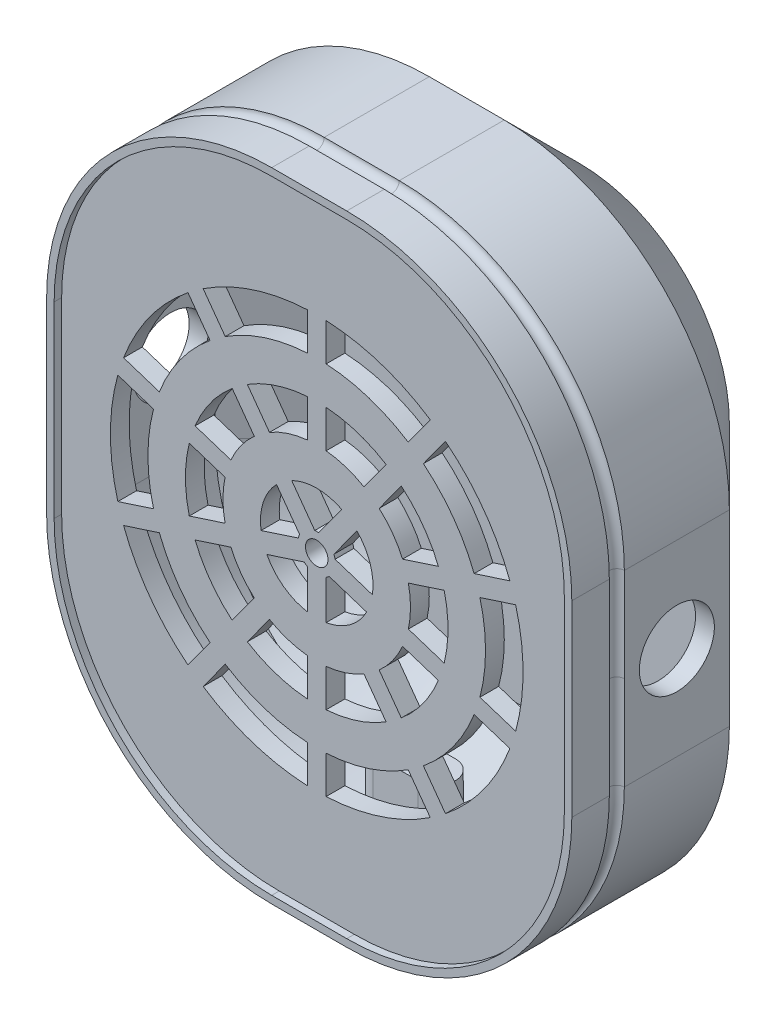
SolidWorks part; units mm, degrees
ref_plane "Front Plane" through (0, 0, 0) normal (0, 0, 1) x (1, 0, 0)
ref_plane "Top Plane" through (0, 0, 0) normal (0, 1, 0) x (1, 0, 0)
ref_plane "Right Plane" through (0, 0, 0) normal (1, 0, 0) x (0, 0, -1)
sketch "Sketch2" plane through (0, 0, 0) normal (0, 0, 1) x (1, 0, 0)
  line L1 (5, -42.5) -> (-5, -42.5)
  line L2 (35, -12.5) -> (35, 12.5)
  line L3 (5, 42.5) -> (-5, 42.5)
  line L4 (-35, -12.5) -> (-35, 12.5)
  line L5 (35, -42.5) -> (-35, 42.5) construction
  line L6 (35, 42.5) -> (-35, -42.5) construction
  arc A0 (-5, -42.5) -> (-35, -12.5) centre (-5, -12.5) cw
  arc A1 (5, -42.5) -> (35, -12.5) centre (5, -12.5) ccw
  arc A2 (35, 12.5) -> (5, 42.5) centre (5, 12.5) ccw
  arc A3 (-5, 42.5) -> (-35, 12.5) centre (-5, 12.5) ccw
  point P0 (0, 0)
  dimension "D1" = 30
extrude "Boss-Extrude1" add sketch "Sketch2" along normal blind 20
sketch "Sketch3" plane through (0, 0, 0) normal (0, 0, -1) x (-1, 0, 0)
  line L8 (25, -12.5) -> (25, 12.5)
  line L9 (5, 32.5) -> (-5, 32.5)
  line L10 (-25, 12.5) -> (-25, -12.5)
  line L11 (-5, -32.5) -> (5, -32.5)
  line L12 (25, -12.5) -> (25, 12.5)
  line L13 (5, 32.5) -> (-5, 32.5)
  line L14 (-25, 12.5) -> (-25, -12.5)
  line L15 (-5, -32.5) -> (5, -32.5)
  arc A8 (5, -32.5) -> (25, -12.5) centre (5, -12.5) ccw
  arc A9 (25, 12.5) -> (5, 32.5) centre (5, 12.5) ccw
  arc A10 (-5, 32.5) -> (-25, 12.5) centre (-5, 12.5) ccw
  arc A11 (-25, -12.5) -> (-5, -32.5) centre (-5, -12.5) ccw
  arc A12 (5, -32.5) -> (25, -12.5) centre (5, -12.5) ccw
  arc A13 (25, 12.5) -> (5, 32.5) centre (5, 12.5) ccw
  arc A14 (-5, 32.5) -> (-25, 12.5) centre (-5, 12.5) ccw
  arc A15 (-25, -12.5) -> (-5, -32.5) centre (-5, -12.5) ccw
  dimension "D1" = 10
extrude "Boss-Extrude2" add sketch "Sketch3" along normal blind 10
chamfer "Chamfer1" distance 10 angle 45 8 edges at (0, -32.5, 0) (-19.1421, -26.6421, 0) (19.1421, -26.6421, 0) (-25, 0, 0) (25, 0, 0) (-19.1421, 26.6421, 0) (19.1421, 26.6421, 0) (0, 32.5, 0)
ref_plane "Plane1" through (0, 0, 15) normal (0, 0, 1) x (1, 0, 0)
sketch "Sketch5" plane through (0, 0, 15) normal (0, 0, 1) x (1, 0, 0)
  line L4 (-5, -42.5) -> (5, -42.5)
  line L5 (35, -12.5) -> (35, 12.5)
  line L6 (5, 42.5) -> (-5, 42.5)
  line L7 (-35, 12.5) -> (-35, -12.5)
  line L8 (-5, -42.5) -> (5, -42.5)
  line L9 (35, -12.5) -> (35, 12.5)
  line L10 (5, 42.5) -> (-5, 42.5)
  line L11 (-35, 12.5) -> (-35, -12.5)
  arc A4 (-35, -12.5) -> (-5, -42.5) centre (-5, -12.5) ccw
  arc A5 (5, -42.5) -> (35, -12.5) centre (5, -12.5) ccw
  arc A6 (35, 12.5) -> (5, 42.5) centre (5, 12.5) ccw
  arc A7 (-5, 42.5) -> (-35, 12.5) centre (-5, 12.5) ccw
  arc A8 (-35, -12.5) -> (-5, -42.5) centre (-5, -12.5) ccw
  arc A9 (5, -42.5) -> (35, -12.5) centre (5, -12.5) ccw
  arc A10 (35, 12.5) -> (5, 42.5) centre (5, 12.5) ccw
  arc A11 (-5, 42.5) -> (-35, 12.5) centre (-5, 12.5) ccw
  dimension "D1" = 0
sketch "Sketch6" plane through (0, 0, 0) normal (0, 1, 0) x (1, 0, 0)
  line L0 (5, -15) -> (35, -15) construction
  line L1 (5, -15) -> (35, -15) construction
  circle A0 centre (35, -15) radius 1
  dimension "D1" = 2
sweep "Cut-Sweep1" cut profiles "Sketch6" path "Sketch5"
shell "Shell1" thickness 2.5
sketch "Sketch8" plane through (0, 0, 20) normal (0, 0, 1) x (1, 0, 0)
  line L4 (-35, 12.5) -> (-10.6269, 12.5) construction
  line L5 (0, 17.5) -> (0, 27.5) construction
  line L7 (15.1361, 22.9597) -> (0.2613, 2.4863)
  line L9 (-1.25, 27.4716) -> (-1.25, 7.3951)
  line L11 (1.25, 27.4716) -> (1.25, 7.3951)
  line L12 (17.1587, 21.4902) -> (2.2839, 1.0168)
  line L13 (25.7408, 9.678) -> (6.6469, 3.474)
  line L14 (26.5133, 7.3004) -> (7.4194, 1.0964)
  line L15 (26.5133, -7.3004) -> (2.4454, 0.5198)
  line L16 (25.7408, -9.678) -> (1.6728, -1.8579)
  line L17 (17.1587, -21.4902) -> (5.358, -5.248)
  line L18 (15.1361, -22.9597) -> (3.3355, -6.7175)
  line L19 (1.25, -27.4716) -> (1.25, -2.1651)
  line L20 (-1.25, -27.4716) -> (-1.25, -2.1651)
  line L21 (-15.1361, -22.9597) -> (-3.3355, -6.7175)
  line L22 (-17.1587, -21.4902) -> (-5.358, -5.248)
  line L23 (-25.7408, -9.678) -> (-1.6728, -1.8579)
  line L24 (-26.5133, -7.3004) -> (-2.4454, 0.5198)
  line L25 (-26.5133, 7.3004) -> (-7.4194, 1.0964)
  line L26 (-25.7408, 9.678) -> (-6.6469, 3.474)
  line L27 (-17.1587, 21.4902) -> (-2.2839, 1.0168)
  line L28 (-15.1361, 22.9597) -> (-0.2613, 2.4863)
  line L29 (-7.5367, 12.5) -> (0, 12.5) construction
  line L30 (1.25, 12.5) -> (7.5367, 12.5) construction
  line L31 (10.6269, 12.5) -> (35, 12.5) construction
  circle A0 centre (0, 0) radius 2.5
  arc A1 (1.25, -7.3951) -> (3.3355, -6.7175) centre (0, 0) ccw
  arc A2 (1.25, -12.4373) -> (6.2992, -10.7968) centre (0, 0) ccw
  arc A3 (1.25, -17.4553) -> (9.2487, -14.8564) centre (0, 0) ccw
  circle A4 centre (0, 0) radius 7.5
  arc A8 (1.25, -22.4653) -> (20.9795, -8.131) centre (0, 0) ccw
  circle A9 centre (0, 0) radius 27.5
  circle A10 centre (0, 0) radius 27.5
  circle A11 centre (0, 0) radius 27.5
  circle A12 centre (0, 0) radius 27.5
  circle A13 centre (0, 0) radius 27.5
  circle A14 centre (0, 0) radius 27.5
  circle A15 centre (0, 0) radius 27.5
  circle A16 centre (0, 0) radius 27.5
  circle A17 centre (0, 0) radius 27.5
  circle A18 centre (0, 0) radius 27.5
  circle A19 centre (0, 0) radius 7.5 construction
  circle A20 centre (0, 0) radius 12.5 construction
  circle A21 centre (0, 0) radius 17.5 construction
  circle A22 centre (0, 0) radius 22.5 construction
  arc A23 (-6.6469, -3.474) -> (-5.358, -5.248) centre (0, 0) ccw
  arc A24 (-11.4423, -5.0322) -> (-8.3218, -9.3273) centre (0, 0) ccw
  arc A25 (-16.2147, -6.5828) -> (-11.2712, -13.3869) centre (0, 0) ccw
  arc A26 (-20.9795, -8.131) -> (-14.216, -17.44) centre (0, 0) ccw
  arc A27 (-3.3355, -6.7175) -> (-1.25, -7.3951) centre (0, 0) ccw
  arc A28 (-6.2992, -10.7968) -> (-1.25, -12.4373) centre (0, 0) ccw
  arc A29 (-9.2487, -14.8564) -> (-1.25, -17.4553) centre (0, 0) ccw
  arc A30 (-12.1935, -18.9095) -> (-1.25, -22.4653) centre (0, 0) ccw
  arc A31 (-7.4194, 1.0964) -> (-7.4194, -1.0964) centre (0, 0) ccw
  arc A32 (-12.2149, 2.6545) -> (-12.2149, -2.6545) centre (0, 0) ccw
  arc A33 (-16.9872, 4.2052) -> (-16.9872, -4.2052) centre (0, 0) ccw
  arc A34 (-21.752, 5.7533) -> (-21.752, -5.7533) centre (0, 0) ccw
  arc A35 (-5.358, 5.248) -> (-6.6469, 3.474) centre (0, 0) ccw
  arc A36 (-8.3218, 9.3273) -> (-11.4423, 5.0322) centre (0, 0) ccw
  arc A37 (-11.2712, 13.3869) -> (-16.2147, 6.5828) centre (0, 0) ccw
  arc A38 (-14.216, 17.44) -> (-20.9795, 8.131) centre (0, 0) ccw
  arc A39 (-1.25, 7.3951) -> (-3.3355, 6.7175) centre (0, 0) ccw
  arc A40 (0, 12.5) -> (-6.2992, 10.7968) centre (0, 0) ccw
  arc A41 (-1.25, 17.4553) -> (-9.2487, 14.8564) centre (0, 0) ccw
  arc A42 (-1.25, 22.4653) -> (-12.1935, 18.9095) centre (0, 0) ccw
  arc A43 (3.3355, 6.7175) -> (1.25, 7.3951) centre (0, 0) ccw
  arc A44 (6.2992, 10.7968) -> (1.25, 12.4373) centre (0, 0) ccw
  arc A45 (9.2487, 14.8564) -> (0, 17.5) centre (0, 0) ccw
  arc A46 (12.1935, 18.9095) -> (0, 22.5) centre (0, 0) ccw
  arc A47 (6.6469, 3.474) -> (5.358, 5.248) centre (0, 0) ccw
  arc A48 (11.4423, 5.0322) -> (8.3218, 9.3273) centre (0, 0) ccw
  arc A49 (16.2147, 6.5828) -> (11.2712, 13.3869) centre (0, 0) ccw
  arc A50 (20.9795, 8.131) -> (14.216, 17.44) centre (0, 0) ccw
  arc A51 (7.4194, -1.0964) -> (7.4194, 1.0964) centre (0, 0) ccw
  arc A52 (12.2149, -2.6545) -> (12.2149, 2.6545) centre (0, 0) ccw
  arc A53 (16.9872, -4.2052) -> (16.9872, 4.2052) centre (0, 0) ccw
  arc A54 (21.752, -5.7533) -> (21.752, 5.7533) centre (0, 0) ccw
  arc A55 (5.358, -5.248) -> (6.6469, -3.474) centre (0, 0) ccw
  arc A56 (8.3218, -9.3273) -> (11.4423, -5.0322) centre (0, 0) ccw
  arc A57 (11.2712, -13.3869) -> (16.2147, -6.5828) centre (0, 0) ccw
  circle A58 centre (0, 0) radius 1.5
  point P71 (0, 0)
  dimension "D1" = 5
  dimension "D7" = 1
  dimension "D6" = 1.25
  dimension "D2" = 5
  dimension "D3" = 5
  dimension "D4" = 5
  dimension "D5" = 5
  dimension "D8" = 10
extrude "Cut-Extrude3" cut sketch "Sketch8" against normal blind 5 contours A34 L25 A9 L24 | L25 A33 L24 A32 | A38 L27 A9 L26 | L27 A37 L26 A36 | A42 L9 A9 L28 | L9 A41 L28 A40 | A46 L7 A9 L11 | L7 A45 L11 A44 | A50 L13 A9 L12 | L13 A49 L12 A48 | L15 A53 L14 A52 | A54 L15 A9 L14 | L17 A9 L16 A8 | L17 A57 L16 A56 | L19 A3 L18 A2 | L21 A29 L20 A28 | A30 L21 A9 L20 | L19 A9 L18 A8 | A26 L23 A9 L22 | L23 A25 L22 A24 | A58 region at (7.666, 23.5936, 20) region at (20.0699, 14.5817, 20) region at (4.6518, 14.3167, 20) region at (-7.666, 23.5936, 20) region at (12.1785, 8.8482, 20) region at (24.8078, 0, 20) region at (-4.6518, 14.3167, 20) region at (-20.0699, 14.5817, 20) region at (15.0535, 0, 20) region at (20.0699, -14.5817, 20) region at (-12.1785, 8.8482, 20) region at (-24.8078, 0, 20) region at (12.1785, -8.8482, 20) region at (7.666, -23.5936, 20) region at (-15.0535, 0, 20) region at (-20.0699, -14.5817, 20) region at (4.6518, -14.3167, 20) region at (-7.666, -23.5936, 20) region at (-12.1785, -8.8482, 20) region at (-4.6518, -14.3167, 20) region at (0, 0, 20)
extrude "Cut-Extrude4" cut sketch "Sketch8<5>" against normal blind 5 contours A4 L24 A0 L27 | A4 L28 A0 L7 | A4 L12 A0 L15 | A1 A4 L16 A0 L19 | A4 L20 A0 L23 region at (0, 5.5485, 20) region at (5.2769, 1.7146, 20) region at (-5.2769, 1.7146, 20) region at (3.2613, -4.4888, 20) region at (-3.2613, -4.4888, 20)
sketch "Sketch8<5>" plane through (0, 0, 20) normal (0, 0, 1) x (1, 0, 0) same geometry as "Sketch8"
sketch "Sketch9" plane through (-35, 0, 0) normal (-1, 0, 0) x (0, 0, 1)
  line L0 (0, 12.5) -> (14, -12.5) construction
  circle A0 centre (7, 0) radius 5
extrude "Cut-Extrude5" cut sketch "Sketch9" against normal through all both and the other way through all
sketch "Sketch10" plane through (-35, 0, 0) normal (-1, 0, 0) x (0, 0, 1)
  line L0 (7, 12.5) -> (7, 15.6961) construction
  line L1 (14, 12.5) -> (0, 12.5) construction
  line L2 (6, 12.5) -> (6, 15.6961)
  line L3 (8, 12.5) -> (8, 15.6961)
  arc A0 (6, 12.5) -> (8, 12.5) centre (7, 12.5) ccw
  arc A1 (8, 15.6961) -> (6, 15.6961) centre (7, 15.6961) ccw
  point P4 (7, 14.098)
extrude "Cut-Extrude6" cut sketch "Sketch10" against normal blind 5 and the other way through all
sketch "Sketch11" plane through (0, -42.5, 0) normal (0, -1, 0) x (1, 0, 0)
  line L0 (-5, 14) -> (5, 0) construction
  line L1 (3, 7) -> (-3, 7) construction
  line L3 (3, 5.5) -> (-3, 5.5)
  line L4 (3, 8.5) -> (-3, 8.5)
  arc A0 (3, 5.5) -> (3, 8.5) centre (3, 7) ccw
  arc A1 (-3, 8.5) -> (-3, 5.5) centre (-3, 7) ccw
  circle A2 centre (8.2801, 7) radius 0.5
  point P8 (0, 7)
  dimension "D1" = 6
extrude "Cut-Extrude7" cut sketch "Sketch11" against normal blind 5
sketch "Sketch12" plane through (0, -40, 0) normal (0, 1, 0) x (1, 0, 0)
  line L0 (3, -5.5) -> (-3, -5.5) construction
  line L1 (3, -5.5) -> (-3, -5.5)
  line L2 (-3, -8.5) -> (3, -8.5) construction
  line L3 (-3, -8.5) -> (3, -8.5)
  line L4 (3, -4.5) -> (-3, -4.5)
  line L5 (-3, -9.5) -> (3, -9.5)
  arc A0 (-3, -5.5) -> (-3, -8.5) centre (-3, -7) ccw construction
  arc A1 (-3, -5.5) -> (-3, -8.5) centre (-3, -7) ccw
  arc A2 (3, -8.5) -> (3, -5.5) centre (3, -7) ccw construction
  arc A3 (3, -8.5) -> (3, -5.5) centre (3, -7) ccw
  arc A4 (-3, -4.5) -> (-3, -9.5) centre (-3, -7) ccw
  arc A5 (3, -9.5) -> (3, -4.5) centre (3, -7) ccw
  dimension "D1" = 1
extrude "Boss-Extrude4" add sketch "Sketch12" along normal blind 10
sketch "Sketch13" plane through (0, -30, 0) normal (0, 1, 0) x (1, 0, 0)
  line L2 (3, -4.5) -> (-3, -4.5)
  line L3 (-3, -9.5) -> (3, -9.5)
  line L4 (3, -4.5) -> (-3, -4.5)
  line L5 (-3, -9.5) -> (3, -9.5)
  arc A2 (3, -9.5) -> (3, -4.5) centre (3, -7) ccw
  arc A3 (-3, -4.5) -> (-3, -9.5) centre (-3, -7) ccw
  arc A4 (3, -9.5) -> (3, -4.5) centre (3, -7) ccw
  arc A5 (-3, -4.5) -> (-3, -9.5) centre (-3, -7) ccw
  dimension "D1" = 0
extrude "Boss-Extrude5" add sketch "Sketch13" against normal blind 1
sketch "Sketch14" plane through (0, -31, 0) normal (0, -1, 0) x (1, 0, 0)
  line L8 (-3, 6.5) -> (3, 6.5)
  line L9 (3, 7.5) -> (-3, 7.5)
  line L10 (-3, 6.5) -> (3, 6.5)
  line L11 (3, 7.5) -> (-3, 7.5)
  arc A8 (3, 6.5) -> (3, 7.5) centre (3, 7) ccw
  arc A9 (-3, 7.5) -> (-3, 6.5) centre (-3, 7) ccw
  arc A10 (3, 6.5) -> (3, 7.5) centre (3, 7) ccw
  arc A11 (-3, 7.5) -> (-3, 6.5) centre (-3, 7) ccw
  dimension "D1" = 1
extrude "Boss-Extrude6" add sketch "Sketch14" along normal up to surface (11.5 mm away) up to face at (0, -42.5, 7)
sketch "Sketch15" plane through (0, -31, 0) normal (0, -1, 0) x (1, 0, 0)
  line L6 (-3, 5.6) -> (3, 5.6)
  line L7 (3, 8.4) -> (-3, 8.4)
  line L8 (-3, 5.6) -> (3, 5.6)
  line L9 (3, 8.4) -> (-3, 8.4)
  line L12 (-3, 5.7) -> (3, 5.7)
  line L13 (3, 8.3) -> (-3, 8.3)
  line L14 (-3, 5.7) -> (3, 5.7)
  line L15 (3, 8.3) -> (-3, 8.3)
  arc A6 (3, 5.6) -> (3, 8.4) centre (3, 7) ccw
  arc A7 (-3, 8.4) -> (-3, 5.6) centre (-3, 7) ccw
  arc A8 (3, 5.6) -> (3, 8.4) centre (3, 7) ccw
  arc A9 (-3, 8.4) -> (-3, 5.6) centre (-3, 7) ccw
  arc A12 (3, 5.7) -> (3, 8.3) centre (3, 7) ccw
  arc A13 (-3, 8.3) -> (-3, 5.7) centre (-3, 7) ccw
  arc A14 (3, 5.7) -> (3, 8.3) centre (3, 7) ccw
  arc A15 (-3, 8.3) -> (-3, 5.7) centre (-3, 7) ccw
  dimension "D1" = 0.1
  dimension "D2" = 0.2
extrude "Boss-Extrude7" add sketch "Sketch15" along normal up to surface (11.5 mm away) up to face at (0, -42.5, 7)
sketch "Sketch16" plane through (0, 0, 20) normal (0, 0, 1) x (1, 0, 0)
  line L8 (-5, -41.5) -> (5, -41.5)
  line L9 (34, -12.5) -> (34, 12.5)
  line L10 (5, 41.5) -> (-5, 41.5)
  line L11 (-34, 12.5) -> (-34, -12.5)
  line L12 (-5, -41.5) -> (5, -41.5)
  line L13 (34, -12.5) -> (34, 12.5)
  line L14 (5, 41.5) -> (-5, 41.5)
  line L15 (-34, 12.5) -> (-34, -12.5)
  line L16 (-5, -42.5) -> (5, -42.5)
  line L17 (35, -12.5) -> (35, 12.5)
  line L18 (5, 42.5) -> (-5, 42.5)
  line L19 (-35, 12.5) -> (-35, -12.5)
  line L20 (-5, -42.5) -> (5, -42.5)
  line L21 (35, -12.5) -> (35, 12.5)
  line L22 (5, 42.5) -> (-5, 42.5)
  line L23 (-35, 12.5) -> (-35, -12.5)
  arc A8 (-34, -12.5) -> (-5, -41.5) centre (-5, -12.5) ccw
  arc A9 (5, -41.5) -> (34, -12.5) centre (5, -12.5) ccw
  arc A10 (34, 12.5) -> (5, 41.5) centre (5, 12.5) ccw
  arc A11 (-5, 41.5) -> (-34, 12.5) centre (-5, 12.5) ccw
  arc A12 (-34, -12.5) -> (-5, -41.5) centre (-5, -12.5) ccw
  arc A13 (5, -41.5) -> (34, -12.5) centre (5, -12.5) ccw
  arc A14 (34, 12.5) -> (5, 41.5) centre (5, 12.5) ccw
  arc A15 (-5, 41.5) -> (-34, 12.5) centre (-5, 12.5) ccw
  arc A16 (-35, -12.5) -> (-5, -42.5) centre (-5, -12.5) ccw
  arc A17 (5, -42.5) -> (35, -12.5) centre (5, -12.5) ccw
  arc A18 (35, 12.5) -> (5, 42.5) centre (5, 12.5) ccw
  arc A19 (-5, 42.5) -> (-35, 12.5) centre (-5, 12.5) ccw
  arc A20 (-35, -12.5) -> (-5, -42.5) centre (-5, -12.5) ccw
  arc A21 (5, -42.5) -> (35, -12.5) centre (5, -12.5) ccw
  arc A22 (35, 12.5) -> (5, 42.5) centre (5, 12.5) ccw
  arc A23 (-5, 42.5) -> (-35, 12.5) centre (-5, 12.5) ccw
  dimension "D1" = 1
  dimension "D2" = 0
extrude "Boss-Extrude8" add sketch "Sketch16" along normal blind 1
